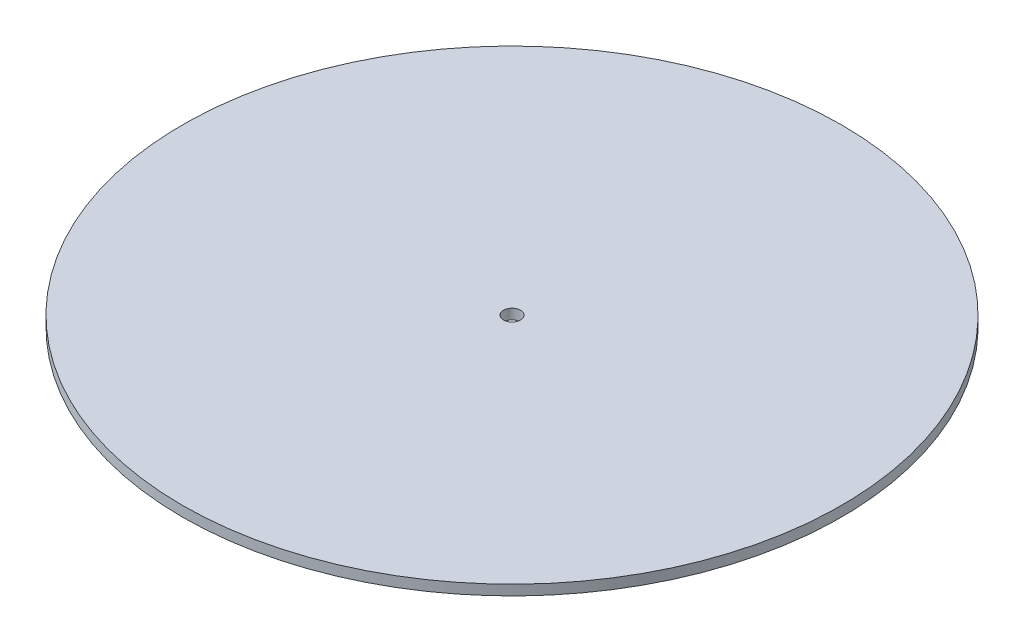
SolidWorks part; units mm, degrees
ref_plane "Front Plane" through (0, 0, 0) normal (0, 0, 1) x (1, 0, 0)
ref_plane "Top Plane" through (0, 0, 0) normal (0, 1, 0) x (1, 0, 0)
ref_plane "Right Plane" through (0, 0, 0) normal (1, 0, 0) x (0, 0, -1)
ref_axis "Axe1" through (0, 55, 0) along (0, -1, 0)
sketch "Esquisse2" plane through (0, 0, 0) normal (0, 0, 1) x (1, 0, 0)
  line L0 (0, 0) -> (97, 0)
  line L1 (97, 0) -> (97, 3)
  line L4 (97, 3) -> (0, 3)
  line L5 (0, 55) -> (0, -55) construction
  line L6 (0, 3) -> (0, 0)
  point P5 (97, 3)
  point P9 (97.7639, 3)
  dimension "D1" = 97
  dimension "D3" = 3
revolve "Révolution1" add sketch "Esquisse2" angle 360 about axis through (0, 55, 0) along (0, -1, 0)
sketch "Esquisse4" plane through (0, 3, 0) normal (0, 1, 0) x (1, 0, 0)
  circle A0 centre (0, 0) radius 2.5
  dimension "D1" = 5
extrude "Enlèv. mat.-Extru.6" cut sketch "Esquisse4" against normal through all
